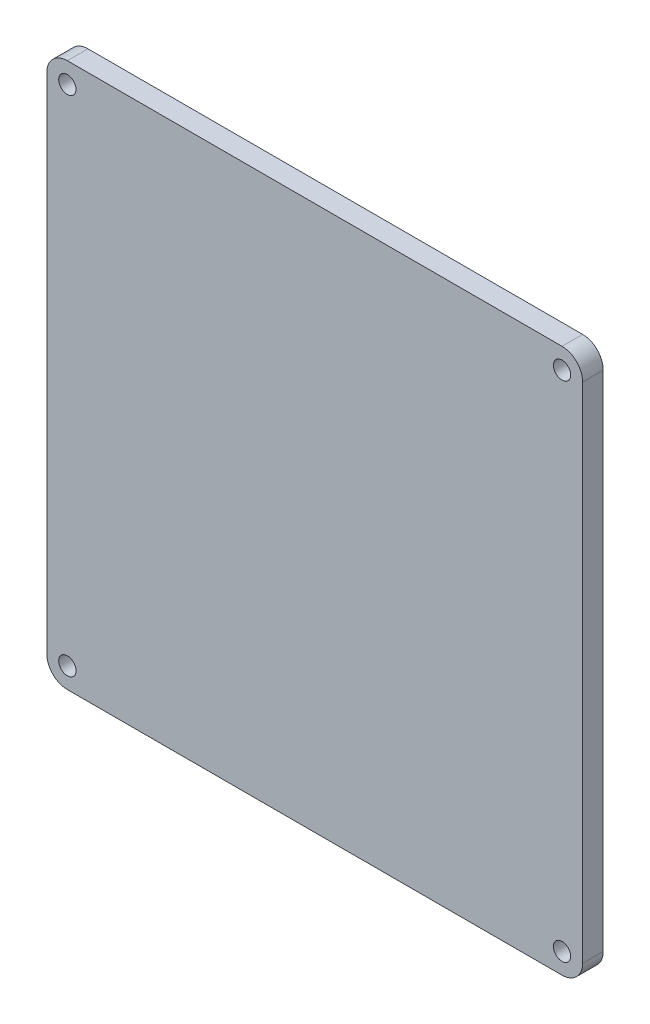
SolidWorks part; units mm, degrees
ref_plane "前视基准面" through (0, 0, 0) normal (0, 0, 1) x (1, 0, 0)
ref_plane "上视基准面" through (0, 0, 0) normal (0, 1, 0) x (1, 0, 0)
ref_plane "右视基准面" through (0, 0, 0) normal (1, 0, 0) x (0, 0, -1)
sketch "草图1" plane through (0, 0, 0) normal (0, 0, 1) x (1, 0, 0)
  line L5 (-130, -132.125) -> (130, -132.125)
  line L6 (-130, -132.125) -> (-130, 132.125)
  line L7 (-130, 132.125) -> (130, 132.125)
  line L8 (130, -132.125) -> (130, 132.125)
  line L9 (-130, -132.125) -> (130, 132.125) construction
  line L10 (-130, 132.125) -> (130, -132.125) construction
  point P0 (0, 0)
  dimension "D1" = 260
  dimension "D2" = 264.25
extrude "凸台-拉伸1" add sketch "草图1" along normal blind 10
fillet "圆角1" radius 10 4 edges at (130, -132.125, 5) (-130, -132.125, 5) (-130, 132.125, 5) (130, 132.125, 5)
hole_wizard "Ø8.4 (8.4) 直径孔1" positions "草图2" profile "草图3" hole size "Ø8.4" standard "GB" end condition through all
sketch "草图2" plane through (0, 0, 0) normal (0, 0, 1) x (1, 0, 0)
  point P0 (-120, 122.125)
  point P3 (120, 122.125)
  point P6 (120, -122.125)
  point P9 (-120, -122.125)
sketch "草图3" plane through (-120, 122.125, 0) normal (1, 0, 0) x (0, 1, 0)
  line L0 (0, 0) -> (0, 10)
  line L1 (0, 10) -> (4.2, 10)
  line L2 (4.2, 10) -> (4.2, 0)
  line L5 (4.2, 0) -> (0, 0)
  line L11 (0, -6.35) -> (0, 107.95) construction
  dimension "通孔孔直径" = 8.4
  dimension "通孔孔深度" = 10
